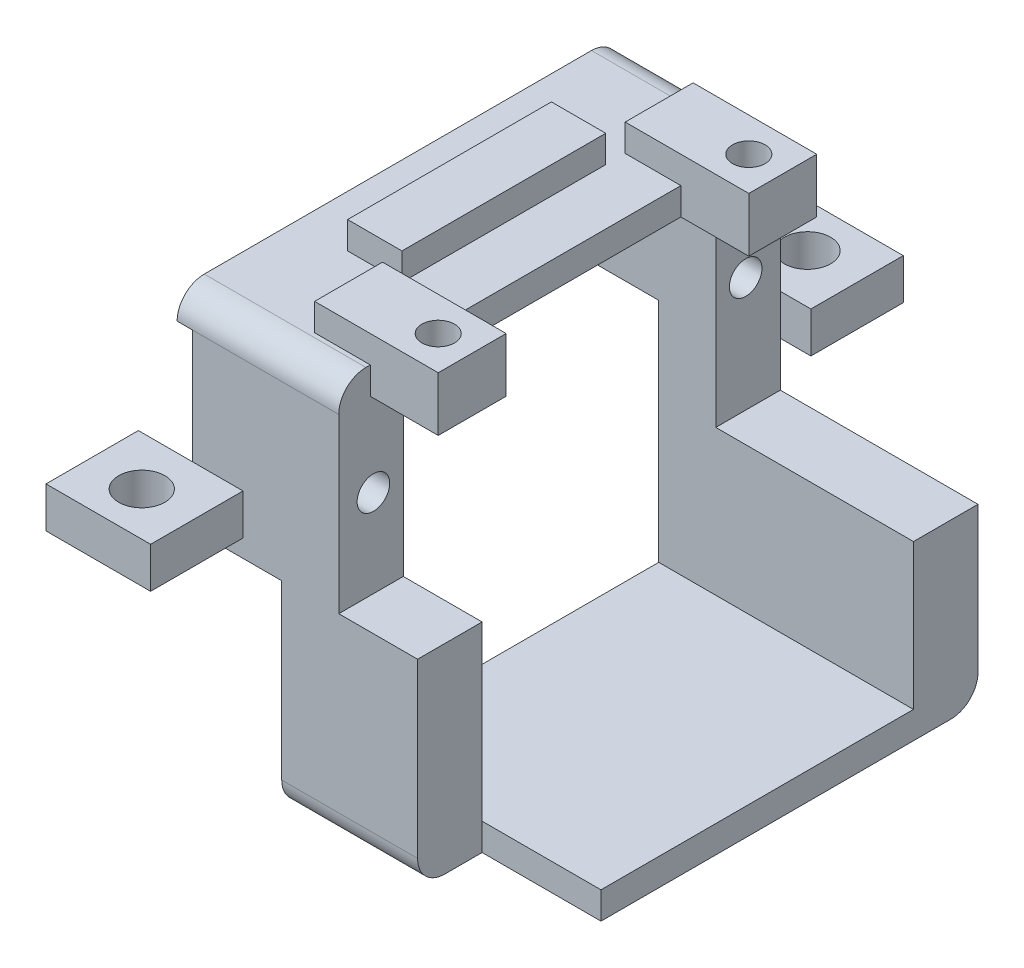
SolidWorks part; units mm, degrees
ref_plane "Front Plane" through (0, 0, 0) normal (0, 0, 1) x (1, 0, 0)
ref_plane "Top Plane" through (0, 0, 0) normal (0, 1, 0) x (1, 0, 0)
ref_plane "Right Plane" through (0, 0, 0) normal (1, 0, 0) x (0, 0, -1)
sketch "Sketch1" plane through (0, 0, 0) normal (0, 1, 0) x (1, 0, 0)
  line L0 (-1.1, 16.25) -> (-1.1, 11.5)
  line L1 (-17.65, -16.25) -> (17.65, -16.25)
  line L2 (-17.65, -16.25) -> (-17.65, 16.25)
  line L3 (-17.65, 16.25) -> (17.65, 16.25)
  line L4 (17.65, -16.25) -> (17.65, 16.25)
  line L5 (-17.65, -16.25) -> (17.65, 16.25) construction
  line L6 (-17.65, 16.25) -> (17.65, -16.25) construction
  line L7 (-1.1, 11.5) -> (17.65, 11.5)
  line L8 (-1.1, -16.25) -> (-1.1, -11.5)
  line L9 (-1.1, -11.5) -> (17.65, -11.5)
  line L10 (-1.1, 11.5) -> (-1.1, -11.5) construction
  line L11 (8.9, -11.5) -> (8.9, -16.25)
  line L12 (-8.8, 16.25) -> (-8.8, 11.5)
  line L13 (-8.8, 11.5) -> (-3.8, 11.5)
  line L14 (-3.8, 11.5) -> (-3.8, 16.25)
  line L15 (-3.8, -16.25) -> (-3.8, -11.5)
  line L16 (-3.8, -11.5) -> (-8.8, -11.5)
  line L17 (-8.8, -11.5) -> (-8.8, -16.25)
  line L18 (-8.8, 11.5) -> (-8.8, -11.5)
  line L19 (5.35, 16.25) -> (5.35, 23.05)
  line L20 (5.35, 23.05) -> (-2.35, 23.05)
  line L21 (-2.35, 23.05) -> (-2.35, 16.25)
  line L22 (-11.65, -16.25) -> (-11.65, -23.05)
  line L23 (-11.65, -23.05) -> (-3.95, -23.05)
  line L24 (-3.95, -23.05) -> (-3.95, -16.25)
  line L25 (9.53, -16.25) -> (9.53, -23.05)
  line L26 (9.53, -23.05) -> (17.23, -23.05)
  line L27 (17.23, -23.05) -> (17.23, -16.25)
  line L28 (-1.1, 11.5) -> (-1.1, -11.5)
  circle A0 centre (1.5, 19.85) radius 1.7
  circle A1 centre (13.38, -19.85) radius 1.7
  circle A2 centre (-7.8, -19.85) radius 1.7
  point P0 (0, 0)
  point P11 (-1.1, 0)
  point P31 (1.5, 23.05)
  point P45 (-7.8, -23.05)
  point P48 (13.38, -23.05)
  dimension "D11" = 3.4
  dimension "D18" = 3.4
  dimension "D19" = 3.4
  dimension "D1" = 32.5
  dimension "D2" = 23
  dimension "D3" = 8.75
  dimension "D4" = 10
  dimension "D5" = 16.55
  dimension "D6" = 2.7
  dimension "D7" = 5
  dimension "D8" = 1.5
  dimension "D9" = 7.7
  dimension "D10" = 6.8
  dimension "D12" = 9.85
  dimension "D13" = 31.03
  dimension "D14" = 7.7
  dimension "D15" = 19.85
  dimension "D16" = 7.7
  dimension "D17" = 6.8
  dimension "D20" = 19.85
extrude "Boss-Extrude1" add sketch "Sketch1" against normal blind 2 contours L7 L28 L9 L4 | L0 L7 L4 L3 | L11 L9 L8 L1 region at (8.275, 0, -13.875) region at (8.275, 0, 0) region at (3.9, 0, 13.875)
extrude "Boss-Extrude2" add sketch "Sketch1<3>" along normal blind 12.7 contours L0 L7 L4 L3 | L11 L9 L8 L1 region at (8.275, 0, -13.875) region at (3.9, 0, 13.875)
sketch "Sketch1<3>" plane through (0, 0, 0) normal (0, 1, 0) x (1, 0, 0) same geometry as "Sketch1"
sketch "Sketch3" plane through (0, 0, 0) normal (0, 1, 0) x (1, 0, 0)
  line L0 (3.1, 16.25) -> (3.1, 11.5)
  line L1 (-17.65, 16.25) -> (17.65, 16.25) construction
  line L2 (-1.1, 11.5) -> (17.65, 11.5) construction
  line L3 (3.1, 11.5) -> (-17.65, 11.5)
  line L4 (-17.65, -16.25) -> (-17.65, 16.25) construction
  line L5 (3.1, -16.25) -> (3.1, -11.5)
  line L6 (-17.65, -16.25) -> (17.65, -16.25) construction
  line L7 (-1.1, -11.5) -> (17.65, -11.5) construction
  line L8 (3.1, -11.5) -> (-17.65, -11.5)
  line L9 (3.1, 11.5) -> (3.1, -11.5)
  line L10 (-7.65, -11.5) -> (-7.65, -16.275)
  line L11 (3.1, 16.25) -> (-17.65, 16.25)
  line L12 (-17.65, 16.25) -> (-17.65, 11.5)
  line L13 (-17.65, -11.5) -> (-17.65, -16.25)
  line L14 (-17.65, -16.25) -> (3.1, -16.25)
  line L15 (-8.8, 11.5) -> (-8.8, -11.5)
  line L16 (-8.8, 11.5) -> (-8.8, 16.25)
  line L17 (-8.8, -11.5) -> (-8.8, -16.25)
  dimension "D1" = 20.75
  dimension "D2" = 10
extrude "Boss-Extrude3" add sketch "Sketch3" along normal blind 12.7 from surface contours L11 L12 L3 L0 | L10 L14 L5 L8 region at (-2.85, 0, -13.875) region at (-2.275, 0, 13.875) starting at face at (8.275, 12.7, -13.875)
extrude "Boss-Extrude4" add sketch "Sketch3<3>" along normal blind 2 from surface contours L16 L3 L0 L11 | L3 L15 L8 L9 | L10 L14 L5 L8 | L8 L17 L14 L10 region at (-2.85, 0, -13.875) region at (-2.85, 0, 0) region at (-2.275, 0, 13.875) region at (-8.225, 0, 13.875) starting at face at (-2.275, 25.4, 13.875)
sketch "Sketch3<3>" plane through (0, 0, 0) normal (0, 1, 0) x (1, 0, 0) same geometry as "Sketch3"
sketch "Sketch2" plane through (0, 0, 0) normal (1, 0, 0) x (0, 0, -1)
  line L0 (13.7, 6.45) -> (-13.7, 6.45) construction
  line L1 (-13.7, 19.15) -> (13.7, 19.15) construction
  circle A0 centre (13.7, 6.45) radius 1.2
  circle A1 centre (-13.7, 6.45) radius 1.2
  circle A2 centre (-13.7, 19.15) radius 1.2
  circle A3 centre (13.7, 19.15) radius 1.2
  point P4 (0, 6.45)
  dimension "D1" = 2.4
  dimension "D2" = 2.4
  dimension "D6" = 2.4
  dimension "D7" = 2.4
  dimension "D3" = 27.4
  dimension "D4" = 6.45
  dimension "D5" = 6.45
extrude "Cut-Extrude1" cut sketch "Sketch2" along normal blind 8 from surface contours A1 | A0 region at (0, 6.45, -13.7) region at (0, 6.45, 13.7) starting at face at (-1.1, 5.85, 0)
extrude "Cut-Extrude2" cut sketch "Sketch2<3>" against normal blind 8 from surface contours A3 | A2 region at (0, 19.15, 13.7) region at (0, 19.15, -13.7) starting at face at (3.1, 19.55, 0)
sketch "Sketch2<3>" plane through (0, 0, 0) normal (1, 0, 0) x (0, 0, -1) same geometry as "Sketch2"
extrude "Boss-Extrude5" add sketch "Sketch1<4>" against normal blind 3 from offset 17 contours L20 L21 L3 L19 A0 | L23 L24 L1 L22 A2 region at (-1.725, 0, -16.3527) region at (-4.0527, 0, 19.65)
sketch "Sketch1<4>" plane through (0, 0, 0) normal (0, 1, 0) x (1, 0, 0) same geometry as "Sketch1"
fillet "Fillet1" radius 2 4 edges at (3.9, -2, 16.25) (-2.85, 27.4, 16.25) (8.275, -2, -16.25) (-2.85, 27.4, -16.25)
sketch "Sketch5" plane through (0, 0, 0) normal (0, 1, 0) x (1, 0, 0)
  line L1 (17.65, 16.25) -> (3.1, 16.25)
  line L2 (17.65, 16.25) -> (17.65, 11.5)
  line L3 (17.65, 11.5) -> (3.1, 11.5)
  line L4 (3.1, 16.25) -> (3.1, 11.5)
extrude "Cut-Extrude3" cut sketch "Sketch5" against normal blind 2 from surface starting at face at (10.375, 12.7, -13.875)
sketch "Sketch6" plane through (0, 0, 0) normal (0, 1, 0) x (1, 0, 0)
  line L1 (-8.8, 11.5) -> (-1.1, 11.5)
  line L2 (-8.8, 11.5) -> (-8.8, 16.25)
  line L3 (-8.8, 16.25) -> (-1.1, 16.25)
  line L4 (-1.1, 11.5) -> (-1.1, 16.25)
extrude "Cut-Extrude4" cut sketch "Sketch6" along normal blind 4 from surface starting at face at (-4.95, 12.7, -13.875)
sketch "Sketch7" plane through (0, 0, 0) normal (0, 1, 0) x (1, 0, 0)
  line L0 (5.6, 11.43) -> (5.6, -11.43) construction
  line L2 (3.1, 8.93) -> (8.1, 8.93)
  line L3 (3.1, 8.93) -> (3.1, 13.93)
  line L4 (3.1, 13.93) -> (8.1, 13.93)
  line L5 (8.1, 8.93) -> (8.1, 13.93)
  line L6 (3.1, 8.93) -> (8.1, 13.93) construction
  line L7 (3.1, 13.93) -> (8.1, 8.93) construction
  line L8 (-5, -7.5) -> (-1, -7.5)
  line L9 (3.1, -8.93) -> (8.1, -8.93)
  line L10 (3.1, -8.93) -> (3.1, -13.93)
  line L11 (3.1, -13.93) -> (8.1, -13.93)
  line L12 (8.1, -8.93) -> (8.1, -13.93)
  line L13 (3.1, -8.93) -> (8.1, -13.93) construction
  line L14 (3.1, -13.93) -> (8.1, -8.93) construction
  line L15 (-5, -7.5) -> (-5, 7.5)
  line L16 (3.1, 12.5) -> (3.1, 14.9) construction
  line L17 (-5, 7.5) -> (-1, 7.5)
  line L18 (-1, -7.5) -> (-1, 7.5)
  line L19 (-5, -7.5) -> (-1, 7.5) construction
  line L20 (-5, 7.5) -> (-1, -7.5) construction
  line L22 (3.1, -8.93) -> (-1, -8.93)
  line L23 (3.1, -8.93) -> (3.1, -13.93)
  line L24 (3.1, -13.93) -> (-1, -13.93)
  line L25 (-1, -8.93) -> (-1, -13.93)
  line L26 (3.1, 13.93) -> (-1, 13.93)
  line L27 (3.1, 13.93) -> (3.1, 8.93)
  line L28 (3.1, 8.93) -> (-1, 8.93)
  line L29 (-1, 13.93) -> (-1, 8.93)
  circle A0 centre (5.6, 11.43) radius 1.2
  circle A1 centre (5.6, -11.43) radius 1.2
  point P4 (5.6, 0)
  point P14 (-3, 0)
  dimension "D2" = 2.4
  dimension "D3" = 2.4
  dimension "D1" = 22.86
  dimension "D4" = 4
  dimension "D5" = 5
  dimension "D6" = 5
  dimension "D7" = 5
  dimension "D8" = 5
  dimension "D9" = 15
  dimension "D10" = 3
extrude "Boss-Extrude6" add sketch "Sketch7" along normal blind 2 and the other way blind 2 from surface contours L8 L18 L17 L15 | L26 L29 L18 L28 L3 | L2 L5 L4 L3 A0 | L18 L25 L24 L10 L22 | L12 L9 L10 L11 A1 region at (3.1707, 0, -11.43) region at (1.05, 0, -11.43) region at (-3, 0, 0) region at (5.6, 0, 9.0007) region at (1.05, 0, 11.43) starting at face at (-2.85, 27.4, 0)
